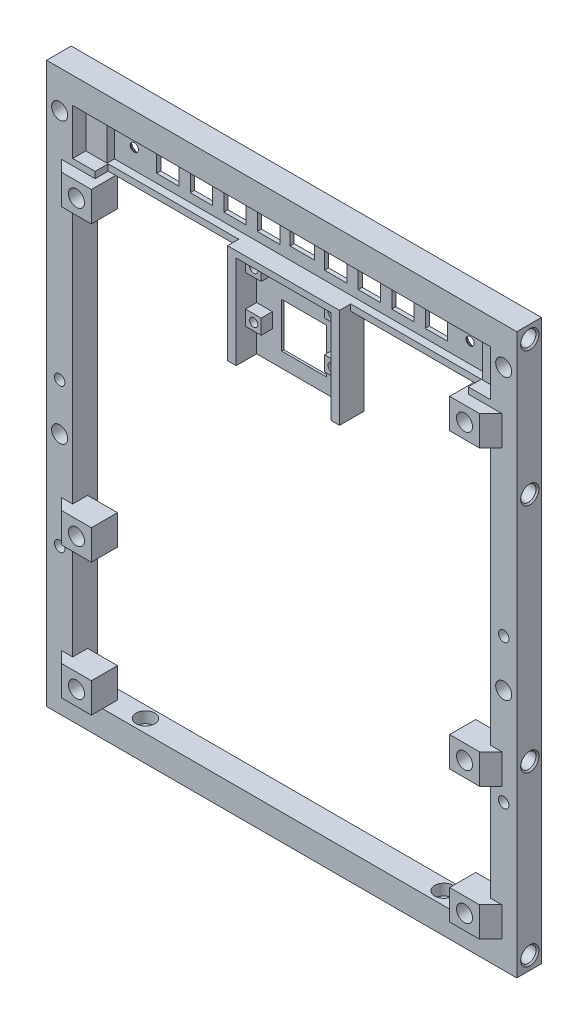
SolidWorks part; units mm, degrees
ref_plane "Front Plane" through (0, 0, 0) normal (0, 0, 1) x (1, 0, 0)
ref_plane "Top Plane" through (0, 0, 0) normal (0, 1, 0) x (1, 0, 0)
ref_plane "Right Plane" through (0, 0, 0) normal (1, 0, 0) x (0, 0, -1)
sketch "Sketch1" plane through (0, 0, 0) normal (0, 0, 1) x (1, 0, 0)
  line L1 (-63, -75) -> (63, -75)
  line L2 (-63, -75) -> (-63, 75)
  line L3 (-63, 75) -> (63, 75)
  line L4 (63, -75) -> (63, 75)
  line L5 (-63, -75) -> (63, 75) construction
  line L6 (-63, 75) -> (63, -75) construction
  line L7 (-56, -68) -> (56, -68)
  line L8 (-56, -68) -> (-56, 68)
  line L9 (-56, 68) -> (56, 68)
  line L10 (56, -68) -> (56, 68)
  line L11 (-56, -68) -> (56, 68) construction
  line L12 (-56, 68) -> (56, -68) construction
  point P0 (0, 0)
  point P6 (0, 0)
  dimension "D1" = 126
  dimension "D2" = 150
  dimension "D3" = 7
  dimension "D4" = 7
extrude "Boss-Extrude1" add sketch "Sketch1" along normal blind 7
sketch "Sketch2" plane through (-63, 0, 0) normal (-1, 0, 0) x (0, 0, 1)
  line L0 (3.5, 71.5) -> (3.5, -71.5) construction
  line L1 (7, 75) -> (0, 75) construction
  circle A0 centre (3.5, -71.5) radius 2.05
  circle A2 centre (3.5, 71.5) radius 2.05
  circle A3 centre (3.5, 35.5) radius 2.05
  circle A4 centre (3.5, -26.5) radius 2.05
  point P2 (3.5, 0)
  point P7 (3.5, 75)
  dimension "D2" = 4.1
  dimension "D3" = 36
  dimension "D4" = 45
  dimension "D1" = 3.5
extrude "Cut-Extrude1" cut sketch "Sketch2" against normal blind 6
mirror "Mirror1" about plane through (0, 0, 0) normal (1, 0, 0) of "Cut-Extrude1"
sketch "Sketch3" plane through (0, -68, 0) normal (0, 1, 0) x (1, 0, 0)
  line L0 (0, 0) -> (0, -7) construction
  line L1 (-56, 0) -> (56, 0) construction
  line L2 (-56, -7) -> (56, -7) construction
  line L3 (40, -3.5) -> (-40, -3.5) construction
  circle A0 centre (40, -3.5) radius 1.35
  circle A1 centre (-40, -3.5) radius 1.35
  point P9 (0, -3.5)
  dimension "D1" = 2.7
  dimension "D2" = 80
extrude "Cut-Extrude2" cut sketch "Sketch3" against normal through all
sketch "Sketch4" plane through (0, -68, 0) normal (0, 1, 0) x (1, 0, 0)
  circle A0 centre (40, -3.5) radius 2.5
  circle A1 centre (-40, -3.5) radius 2.5
  dimension "D1" = 5
extrude "Cut-Extrude3" cut sketch "Sketch4" against normal blind 3
sketch "Sketch5" plane through (0, 0, 0) normal (0, 0, -1) x (-1, 0, 0)
  line L0 (-59.5, -75) -> (-59.5, 75) construction
  line L1 (63, -75) -> (-63, -75) construction
  line L2 (-63, 75) -> (63, 75) construction
  line L3 (-56, 0) -> (-63, 0) construction
  line L4 (-56, -68) -> (-56, 68) construction
  line L5 (-63, -75) -> (-63, 75) construction
  line L6 (0, 75) -> (0, -75) construction
  line L7 (56, -68) -> (-56, -68) construction
  circle A0 centre (-59.5, 2.6) radius 1.4
  circle A1 centre (59.5, 2.6) radius 1.4
  circle A2 centre (-59.5, -36) radius 1.4
  circle A3 centre (59.5, -36) radius 1.4
  point P12 (-59.5, 0)
  point P13 (-59.5, 0)
  dimension "D1" = 2.8
  dimension "D2" = 2.6
  dimension "D3" = 32
extrude "Cut-Extrude4" cut sketch "Sketch5" against normal through all
sketch "Sketch6" plane through (0, 0, 0) normal (0, 0, -1) x (-1, 0, 0)
  circle A0 centre (-59.5, 2.6) radius 2.5
  circle A1 centre (59.5, 2.6) radius 2.5
  circle A2 centre (-59.5, -36) radius 2.5
  circle A3 centre (59.5, -36) radius 2.5
  dimension "D1" = 5
extrude "Cut-Extrude5" cut sketch "Sketch6" against normal blind 3
sketch "Sketch7" plane through (0, 0, 0) normal (0, 0, -1) x (-1, 0, 0)
  line L0 (-56, 68) -> (-63, 68) construction
  line L1 (-63, -75) -> (-63, 75) construction
  line L2 (-59.5, 65) -> (-59.5, -10) construction
  line L3 (-63, 75) -> (63, 75) construction
  circle A0 centre (-59.5, 65) radius 2.15
  circle A1 centre (-59.5, -10) radius 2.15
  point P8 (-59.5, 68)
  dimension "D1" = 4.3
  dimension "D2" = 10
  dimension "D3" = 75
extrude "Cut-Extrude6" cut sketch "Sketch7" against normal through all
mirror "Mirror2" about plane through (0, 0, 0) normal (1, 0, 0) of "Cut-Extrude6"
sketch "Sketch8" plane through (0, 0, 3) normal (0, 0, -1) x (-1, 0, 0)
  line L2 (-60.9, 0.5288) -> (-60.9, 4.6712)
  line L4 (-58.1, 0.5288) -> (-58.1, 4.6712)
  line L5 (-60.9, 0.5288) -> (-58.1, 4.6712) construction
  line L6 (-60.9, 4.6712) -> (-58.1, 0.5288) construction
  line L8 (-60.9, -38.0712) -> (-60.9, -33.9288)
  line L10 (-58.1, -38.0712) -> (-58.1, -33.9288)
  line L11 (-60.9, -38.0712) -> (-58.1, -33.9288) construction
  line L12 (-60.9, -33.9288) -> (-58.1, -38.0712) construction
  circle A0 centre (-59.5, 2.6) radius 2.5 construction
  circle A1 centre (-59.5, -36) radius 2.5 construction
  circle A2 centre (-59.5, -36) radius 2.5 construction
  arc A3 (-58.1, 4.6712) -> (-60.9, 4.6712) centre (-59.5, 2.6) ccw
  arc A4 (-58.1, -33.9288) -> (-60.9, -33.9288) centre (-59.5, -36) ccw
  circle A5 centre (-59.5, 2.6) radius 1.4 construction
  circle A6 centre (-59.5, -36) radius 1.4 construction
  arc A7 (-60.9, -38.0712) -> (-58.1, -38.0712) centre (-59.5, -36) ccw
  arc A8 (-60.9, 0.5288) -> (-58.1, 0.5288) centre (-59.5, 2.6) ccw
  point P0 (-59.5, 2.6)
  point P8 (-59.5, -36)
extrude "Cut-Extrude7" cut sketch "Sketch8" against normal blind 0.2
sketch "Sketch9" plane through (0, 0, 3.2) normal (0, 0, -1) x (-1, 0, 0)
  line L0 (-58.1, 2.6) -> (-58.1, 4.6712) construction
  line L1 (-60.9, 1.2) -> (-58.1, 1.2)
  line L2 (-60.9, 1.2) -> (-60.9, 4)
  line L3 (-60.9, 4) -> (-58.1, 4)
  line L4 (-58.1, 1.2) -> (-58.1, 4)
  line L5 (-60.9, 1.2) -> (-58.1, 4) construction
  line L6 (-60.9, 4) -> (-58.1, 1.2) construction
  line L7 (-58.1, -38.0712) -> (-58.1, -33.9288) construction
  line L8 (-60.9, -37.4) -> (-58.1, -37.4)
  line L9 (-60.9, -37.4) -> (-60.9, -34.6)
  line L10 (-60.9, -34.6) -> (-58.1, -34.6)
  line L11 (-58.1, -37.4) -> (-58.1, -34.6)
  line L12 (-60.9, -37.4) -> (-58.1, -34.6) construction
  line L13 (-60.9, -34.6) -> (-58.1, -37.4) construction
  arc A0 (-58.1, 2.6) -> (-60.9, 2.6) centre (-59.5, 2.6) ccw construction
  point P0 (-59.5, 2.6)
  point P8 (-59.5, -36)
extrude "Cut-Extrude8" cut sketch "Sketch9" against normal blind 0.2
mirror "Mirror3" about plane through (0, 0, 0) normal (1, 0, 0) of "Cut-Extrude8", "Cut-Extrude7"
sketch "Sketch10" plane through (0, 0, 7) normal (0, 0, 1) x (1, 0, 0)
  line L0 (56, -68) -> (56, 68) construction
  line L1 (56, -68) -> (50, -68)
  line L2 (56, -68) -> (56, -62)
  line L3 (56, -62) -> (50, -62)
  line L4 (50, -68) -> (50, -62)
  line L5 (56, -38.5) -> (50, -38.5)
  line L6 (56, -38.5) -> (56, -32.5)
  line L7 (56, -32.5) -> (50, -32.5)
  line L8 (50, -38.5) -> (50, -32.5)
  line L9 (-56, -68) -> (56, -68) construction
  dimension "D1" = 6
  dimension "D2" = 35.5
extrude "Boss-Extrude2" add sketch "Sketch10" against normal offset from surface (5.5 mm away) 1.5 up to face at (-57.35, -10, 0)
sketch "Sketch11" plane through (0, 0, 1.5) normal (0, 0, -1) x (-1, 0, 0)
  line L0 (-56, -38.5) -> (-50, -32.5) construction
  line L2 (-56, -68) -> (-50, -62) construction
  circle A0 centre (-53, -35.5) radius 1.65
  circle A1 centre (-53, -65) radius 1.65
  dimension "D1" = 3.3
extrude "Cut-Extrude9" cut sketch "Sketch11" against normal through all
mirror "Mirror4" about plane through (0, 0, 0) normal (1, 0, 0) of "Cut-Extrude9", "Boss-Extrude2"
sketch "Sketch12" plane through (0, 0, 0) normal (0, 0, -1) x (-1, 0, 0)
  line L0 (56, 68) -> (56, -68) construction
  line L1 (-56, 68) -> (56, 68)
  line L2 (-56, 68) -> (-56, 54)
  line L3 (-56, 54) -> (56, 54)
  line L4 (56, 68) -> (56, 54)
  dimension "D1" = 14
extrude "Boss-Extrude3" add sketch "Sketch12" against normal blind 1.5
sketch "Sketch13" plane through (0, 0, 1.5) normal (0, 0, 1) x (1, 0, 0)
  line L0 (-56, 68) -> (56, 54) construction
  line L2 (-50.3, 55.7) -> (50.3, 55.7)
  line L3 (-50.3, 55.7) -> (-50.3, 66.3)
  line L4 (-50.3, 66.3) -> (50.3, 66.3)
  line L5 (50.3, 55.7) -> (50.3, 66.3)
  line L6 (-50.3, 55.7) -> (50.3, 66.3) construction
  line L7 (-50.3, 66.3) -> (50.3, 55.7) construction
  line L8 (-56, 54) -> (56, 54)
  line L9 (-56, 54) -> (-56, 68)
  line L10 (-56, 68) -> (56, 68)
  line L11 (56, 54) -> (56, 68)
  line L12 (-56, 54) -> (56, 68) construction
  line L13 (-56, 68) -> (56, 54) construction
  point P4 (0, 61)
  point P9 (0, 61)
  dimension "D1" = 100.6
  dimension "D2" = 10.6
extrude "Boss-Extrude4" add sketch "Sketch13" along normal blind 2
sketch "Sketch14" plane through (0, 0, 1.5) normal (0, 0, 1) x (1, 0, 0)
  line L0 (0, 66.3) -> (0, 55.7) construction
  line L1 (50.3, 66.3) -> (-50.3, 66.3) construction
  line L2 (-50.3, 55.7) -> (50.3, 55.7) construction
  line L3 (-50.3, 61) -> (50.3, 61) construction
  line L4 (50.3, 55.7) -> (50.3, 66.3) construction
  line L5 (-33, 64) -> (-39, 64)
  line L6 (-3.25, 59) -> (3.25, 59)
  line L7 (-3.25, 59) -> (-3.25, 63)
  line L8 (-3.25, 63) -> (3.25, 63)
  line L9 (3.25, 59) -> (3.25, 63)
  line L10 (-3.25, 59) -> (3.25, 63) construction
  line L11 (-3.25, 63) -> (3.25, 59) construction
  line L12 (6, 58) -> (12, 58)
  line L13 (6, 58) -> (6, 64)
  line L14 (6, 64) -> (12, 64)
  line L15 (12, 58) -> (12, 64)
  line L16 (6, 58) -> (12, 64) construction
  line L17 (6, 64) -> (12, 58) construction
  line L18 (15, 58) -> (21, 58)
  line L19 (15, 58) -> (15, 64)
  line L20 (15, 64) -> (21, 64)
  line L21 (21, 58) -> (21, 64)
  line L22 (15, 58) -> (21, 64) construction
  line L23 (15, 64) -> (21, 58) construction
  line L24 (24, 58) -> (30, 58)
  line L25 (24, 58) -> (24, 64)
  line L26 (24, 64) -> (30, 64)
  line L27 (30, 58) -> (30, 64)
  line L28 (24, 58) -> (30, 64) construction
  line L29 (24, 64) -> (30, 58) construction
  line L30 (33, 58) -> (39, 58)
  line L31 (33, 58) -> (33, 64)
  line L32 (33, 64) -> (39, 64)
  line L33 (39, 58) -> (39, 64)
  line L34 (33, 58) -> (39, 64) construction
  line L35 (33, 64) -> (39, 58) construction
  line L36 (-39, 58) -> (-39, 64)
  line L37 (-33, 58) -> (-39, 58)
  line L38 (-33, 58) -> (-33, 64)
  line L39 (-24, 64) -> (-30, 64)
  line L40 (-30, 58) -> (-30, 64)
  line L41 (-24, 58) -> (-30, 58)
  line L42 (-24, 58) -> (-24, 64)
  line L43 (-15, 64) -> (-21, 64)
  line L44 (-21, 58) -> (-21, 64)
  line L45 (-15, 58) -> (-21, 58)
  line L46 (-15, 58) -> (-15, 64)
  line L47 (-6, 64) -> (-12, 64)
  line L48 (-12, 58) -> (-12, 64)
  line L49 (-6, 58) -> (-12, 58)
  line L50 (-6, 58) -> (-6, 64)
  circle A0 centre (-45, 61) radius 1.3 construction
  circle A1 centre (45, 61) radius 1.3 construction
  point P6 (0, 61)
  point P11 (0, 61)
  point P16 (9, 61)
  point P21 (18, 61)
  point P26 (27, 61)
  point P31 (36, 61)
  dimension "D10" = 2.6
  dimension "D9" = 45
  dimension "D1" = 6.5
  dimension "D2" = 4
  dimension "D3" = 6
  dimension "D4" = 9
  dimension "D5" = 9
  dimension "D6" = 9
  dimension "D7" = 9
  dimension "D8" = 45
extrude "Cut-Extrude10" cut sketch "Sketch14" against normal through all
sketch "Sketch15" plane through (0, 0, 1.5) normal (0, 0, 1) x (1, 0, 0)
  circle A0 centre (-45, 61) radius 1
  circle A1 centre (45, 61) radius 1
  dimension "D1" = 2
extrude "Boss-Extrude5" add sketch "Sketch15" along normal up to surface (2 mm away) up to face at (0, 61, 3.5)
chamfer "Chamfer1" distance 0.4 angle 45 3 edges at (-56, -7, 0) (56, -7, 0) (0, -68, 0) tangent propagation no
chamfer "Chamfer2" distance 0.4 angle 45 4 edges at (0, 75, 0) (-63, 0, 0) (0, -75, 0) (63, 0, 0)
chamfer "Chamfer3" distance 0.4 angle 45 36 edges at (-36, 58, 0) (-39, 61, 0) (-36, 64, 0) (-33, 61, 0) (-27, 58, 0) (-30, 61, 0) (-27, 64, 0) (-24, 61, 0) (-18, 58, 0) (-21, 61, 0) (-18, 64, 0) (-15, 61, 0) (-9, 58, 0) (-12, 61, 0) (-9, 64, 0) (-6, 61, 0) (0, 59, 0) (-3.25, 61, 0) (0, 63, 0) (3.25, 61, 0) (9, 58, 0) (6, 61, 0) (9, 64, 0) (12, 61, 0) (18, 58, 0) (15, 61, 0) (18, 64, 0) (21, 61, 0) (36, 58, 0) (33, 61, 0) (36, 64, 0) (39, 61, 0) (27, 58, 0) (24, 61, 0) (27, 64, 0) (30, 61, 0)
sketch "Sketch16" plane through (0, 0, 7) normal (0, 0, 1) x (1, 0, 0)
  line L0 (-50, 54) -> (-50, 55.7)
  line L1 (-56, -32.5) -> (-50, -32.5)
  line L2 (-56, -32.5) -> (-56, -26.5)
  line L3 (-56, -26.5) -> (-50, -26.5)
  line L4 (-50, -32.5) -> (-50, -26.5)
  line L5 (56, -32.5) -> (50, -32.5)
  line L6 (56, -32.5) -> (56, -26.5)
  line L7 (56, -26.5) -> (50, -26.5)
  line L8 (50, -32.5) -> (50, -26.5)
  line L9 (56, 54) -> (50, 54) construction
  line L10 (56, 54) -> (56, 48)
  line L11 (56, 48) -> (50, 48)
  line L12 (50, 54) -> (50, 48)
  line L13 (-56, 54) -> (-50, 54) construction
  line L14 (-56, 54) -> (-56, 48)
  line L15 (-56, 48) -> (-50, 48)
  line L16 (-50, 54) -> (-50, 48)
  line L17 (-50.3, 55.7) -> (50.3, 55.7) construction
  line L18 (-50, 55.7) -> (-56, 55.7)
  line L19 (-56, 68) -> (-56, 54) construction
  line L20 (-56, 55.7) -> (-56, 54)
  line L21 (50, 54) -> (50, 55.7)
  line L22 (50, 55.7) -> (56, 55.7)
  line L23 (56, 54) -> (56, 68) construction
  line L24 (56, 55.7) -> (56, 54)
  dimension "D1" = 6
extrude "Boss-Extrude7" add sketch "Sketch16" against normal offset from surface (5.5 mm away) 1.5 up to face at (-36, 61, 0)
sketch "Sketch17" plane through (0, 0, 1.5) normal (0, 0, -1) x (-1, 0, 0)
  line L0 (-50, 48) -> (50, -26.5) construction
  line L1 (-50, -26.5) -> (-50, -38.5) construction
  line L2 (-53, -29.5) -> (53, -29.5) construction
  line L3 (-53, -29.5) -> (-53, 51) construction
  line L4 (-53, 51) -> (53, 51) construction
  line L5 (53, -29.5) -> (53, 51) construction
  line L6 (-53, -29.5) -> (53, 51) construction
  line L7 (-53, 51) -> (53, -29.5) construction
  line L8 (50, -26.5) -> (56, -26.5) construction
  circle A0 centre (-53, -29.5) radius 1.65
  circle A1 centre (53, -29.5) radius 1.65
  circle A2 centre (53, 51) radius 1.65
  circle A3 centre (-53, 51) radius 1.65
  point P4 (0, 10.75)
  dimension "D3" = 3.3
  dimension "D1" = 3
  dimension "D2" = 3
extrude "Cut-Extrude11" cut sketch "Sketch17" against normal through all
sketch "Sketch18" plane through (0, 0, 1.5) normal (0, 0, 1) x (1, 0, 0)
  circle A0 centre (-45, 61) radius 1.1
  circle A1 centre (45, 61) radius 1.1
  dimension "D1" = 2.2
extrude "Cut-Extrude12" cut sketch "Sketch18" against normal through all both and the other way through all
chamfer "Chamfer4" distance 1.3 angle 45 2 edges at (-43.9, 61, 0) (46.1, 61, 0)
sketch "Sketch19" plane through (0, 0, 1.5) normal (0, 0, -1) x (-1, 0, 0)
  line L1 (-56, -68) -> (56, -68)
  line L2 (-56, -68) -> (-56, 54)
  line L3 (-56, 54) -> (56, 54)
  line L4 (56, -68) -> (56, 54)
extrude "Cut-Extrude13" cut sketch "Sketch19" against normal through all
ref_plane "Plane1" through (0, 0, 3) normal (0, 0, 1) x (1, 0, 0)
sketch "Sketch20" plane through (0, 0, 3) normal (0, 0, 1) x (1, 0, 0)
  line L0 (56, 54) -> (56, -68) construction
  line L1 (56, -68) -> (48, -68)
  line L2 (56, -68) -> (56, -60)
  line L3 (56, -60) -> (48, -60)
  line L4 (48, -68) -> (48, -60)
  line L5 (56, 54) -> (48, 54)
  line L6 (56, 54) -> (56, 46)
  line L7 (56, 46) -> (48, 46)
  line L8 (48, 54) -> (48, 46)
  line L9 (56, -24.5) -> (48, -24.5)
  line L10 (56, -24.5) -> (56, -32.5)
  line L11 (56, -32.5) -> (48, -32.5)
  line L12 (48, -24.5) -> (48, -32.5)
  dimension "D1" = 8
  dimension "D2" = 27.5
extrude "Boss-Extrude8" add sketch "Sketch20" along normal blind 7
sketch "Sketch21" plane through (0, 0, 3) normal (0, 0, -1) x (-1, 0, 0)
  line L0 (-48, 54) -> (-56, 46) construction
  line L1 (-56, -60) -> (-48, -68) construction
  line L2 (-56, -24.5) -> (-48, -32.5) construction
  circle A0 centre (-52, 50) radius 2.15
  circle A1 centre (-52, -64) radius 2.15
  circle A2 centre (-52, -28.5) radius 2.15
  dimension "D1" = 4.3
extrude "Cut-Extrude14" cut sketch "Sketch21" against normal through all
mirror "Mirror5" about plane through (0, 0, 0) normal (1, 0, 0) of "Cut-Extrude14", "Boss-Extrude8"
chamfer "Chamfer5" distance 3 angle 45 6 edges at (-56, -64, 7) (56, -64, 7) (56, 50, 7) (-56, 50, 7) (-56, -28.5, 7) (56, -28.5, 7)
sketch "Sketch23" plane through (0, 0, 0) normal (0, 0, -1) x (-1, 0, 0)
  line L0 (-56.4, 54) -> (56.4, 54) construction
  line L1 (-15, 54) -> (15, 54)
  line L2 (-15, 54) -> (-15, 29)
  line L3 (-15, 29) -> (15, 29)
  line L4 (15, 54) -> (15, 29)
  point P6 (0, 29)
  dimension "D1" = 25
  dimension "D2" = 30
extrude "Boss-Extrude10" add sketch "Sketch23" against normal up to surface (3.5 mm away) up to face at (0, 54.5667, 3.5)
sketch "Sketch24" plane through (0, 0, 3.5) normal (0, 0, 1) x (1, 0, 0)
  line L0 (15, 29) -> (-15, 29) construction
  line L1 (-12.7, 29) -> (12.7, 29)
  line L2 (-12.7, 29) -> (-12.7, 54)
  line L3 (-12.7, 54) -> (12.7, 54)
  line L4 (12.7, 29) -> (12.7, 54)
  line L5 (-48, 54) -> (-15, 54) construction
  point P6 (0, 29)
  dimension "D1" = 25.4
extrude "Cut-Extrude15" cut sketch "Sketch24" against normal offset from surface (2.5 mm away) 1 up to face at (-47.4, 61, 0)
sketch "Sketch26" plane through (0, 0, 1) normal (0, 0, 1) x (1, 0, 0)
  line L0 (12.7, 54) -> (-12.7, 54) construction
  line L1 (-12.5, 53.4) -> (12.5, 53.4) construction
  line L2 (-12.5, 53.4) -> (-12.5, 29.538) construction
  line L3 (-12.5, 29.538) -> (12.5, 29.538) construction
  line L4 (12.5, 53.4) -> (12.5, 29.538) construction
  line L5 (0, 53.4) -> (0, 29.538) construction
  line L6 (-10.5, 51.4) -> (10.5, 51.4) construction
  line L7 (-10.5, 51.4) -> (-10.5, 38.9) construction
  line L8 (-10.5, 38.9) -> (10.5, 38.9) construction
  line L9 (10.5, 51.4) -> (10.5, 38.9) construction
  line L10 (12.7, 54) -> (-12.7, 54) construction
  line L11 (-5.4, 33.6) -> (5.4, 33.6) construction
  line L12 (-5.4, 33.6) -> (-5.4, 44.4) construction
  line L13 (-5.4, 44.4) -> (5.4, 44.4) construction
  line L14 (5.4, 33.6) -> (5.4, 44.4) construction
  line L15 (-5.4, 33.6) -> (5.4, 44.4) construction
  line L16 (-5.4, 44.4) -> (5.4, 33.6) construction
  circle A0 centre (-10.5, 51.4) radius 1.1 construction
  circle A1 centre (10.5, 51.4) radius 1.1 construction
  circle A2 centre (10.5, 38.9) radius 1.1 construction
  circle A3 centre (-10.5, 38.9) radius 1.1 construction
  point P4 (0, 53.4)
  point P7 (0, 54)
  point P12 (0, 51.4)
  point P19 (0, 39)
  dimension "D3" = 2.2
  dimension "D1" = 25
  dimension "D2" = 23.862
  dimension "D4" = 2
  dimension "D5" = 14.5
  dimension "D6" = 10.8
  dimension "D7" = 10.8
  dimension "D8" = 14.4
  dimension "D9" = 0.6
  dimension "D10" = 2
sketch "Sketch27" plane through (0, 0, 1) normal (0, 0, 1) x (1, 0, 0)
  line L0 (-12.7, 54) -> (-12.7, 29) construction
  line L1 (-12.7, 54) -> (-8.5, 54)
  line L2 (-12.7, 54) -> (-12.7, 49.4)
  line L3 (-12.7, 49.4) -> (-8.5, 49.4)
  line L4 (-8.5, 54) -> (-8.5, 49.4)
  line L5 (-12.7, 36.9) -> (-8.5, 36.9)
  line L6 (-12.7, 36.9) -> (-12.7, 40.9)
  line L7 (-12.7, 40.9) -> (-8.5, 40.9)
  line L8 (-8.5, 36.9) -> (-8.5, 40.9)
  line L9 (0, 54) -> (0, 29) construction
  line L10 (12.7, 54) -> (-12.7, 54) construction
  line L11 (-12.7, 29) -> (12.7, 29) construction
  line L12 (8.5, 36.9) -> (8.5, 40.9)
  line L13 (12.7, 40.9) -> (8.5, 40.9)
  line L14 (12.7, 36.9) -> (12.7, 40.9)
  line L15 (12.7, 36.9) -> (8.5, 36.9)
  line L16 (8.5, 54) -> (8.5, 49.4)
  line L17 (12.7, 49.4) -> (8.5, 49.4)
  line L18 (12.7, 54) -> (12.7, 49.4)
  line L19 (12.7, 54) -> (8.5, 54)
  dimension "D1" = 2
  dimension "D2" = 2
  dimension "D3" = 2
  dimension "D4" = 2
  dimension "D5" = 2
extrude "Boss-Extrude11" add sketch "Sketch27" along normal blind 3
sketch "Sketch28" plane through (0, 0, 1) normal (0, 0, 1) x (1, 0, 0)
  line L0 (-5.4, 44.4) -> (5.4, 44.4) construction
  line L1 (-6, 33) -> (6, 33)
  line L2 (-6, 33) -> (-6, 45)
  line L3 (-6, 45) -> (6, 45)
  line L4 (6, 33) -> (6, 45)
  line L5 (-6, 33) -> (6, 45) construction
  line L6 (-6, 45) -> (6, 33) construction
  line L7 (5.4, 33.6) -> (5.4, 44.4) construction
  point P0 (0, 39)
  dimension "D1" = 0.6
  dimension "D2" = 0.6
extrude "Cut-Extrude16" cut sketch "Sketch28" against normal through all
sketch "Sketch29" plane through (0, 0, 4) normal (0, 0, 1) x (1, 0, 0)
  circle A0 centre (-10.5, 38.9) radius 1.1
  circle A1 centre (-10.5, 51.4) radius 1.1
  circle A2 centre (10.5, 51.4) radius 1.1
  circle A3 centre (10.5, 38.9) radius 1.1
  dimension "D1" = 2.2
extrude "Cut-Extrude17" cut sketch "Sketch29" against normal through all
chamfer "Chamfer6" distance 1.3 angle 45 4 edges at (11.6, 38.9, 0) (-9.4, 38.9, 0) (-9.4, 51.4, 0) (11.6, 51.4, 0)
chamfer "Chamfer7" distance 0.4 angle 45 4 edges at (0, 33, 0) (-6, 39, 0) (0, 45, 0) (6, 39, 0)
chamfer "Chamfer8" distance 0.4 angle 45 2 edges at (-35.7, 54, 0) (35.7, 54, 0)
sketch "Sketch30" plane through (0, 0, 3.5) normal (0, 0, 1) x (1, 0, 0)
  line L0 (-12.7, 29) -> (-12.7, 54)
  line L1 (-12.7, 54) -> (12.7, 54)
  line L2 (12.7, 54) -> (12.7, 29)
  line L3 (12.7, 29) -> (15, 29)
  line L4 (15, 29) -> (15, 55.7)
  line L5 (-50.3, 55.7) -> (50.3, 55.7) construction
  line L6 (15, 55.7) -> (-15, 55.7)
  line L7 (-15, 55.7) -> (-15, 29)
  line L8 (-12.7, 29) -> (-15, 29)
extrude "Boss-Extrude12" add sketch "Sketch30" along normal blind 3
chamfer "Chamfer9" distance 0.4 angle 45 18 edges at (-49.85, -64, 3) (-57.35, -10, 0) (-49.85, -28.5, 3) (-49.85, 50, 3) (-57.35, 65, 0) (49.85, -64, 3) (49.85, -28.5, 3) (49.85, 50, 3) (57.35, -10, 0) (57.35, 65, 0) (63, 71.5, 5.55) (63, 35.5, 5.55) (63, -26.5, 5.55) (63, -71.5, 5.55) (-63, -71.5, 5.55) (-63, -26.5, 5.55) (-63, 35.5, 5.55) (-63, 71.5, 5.55)
